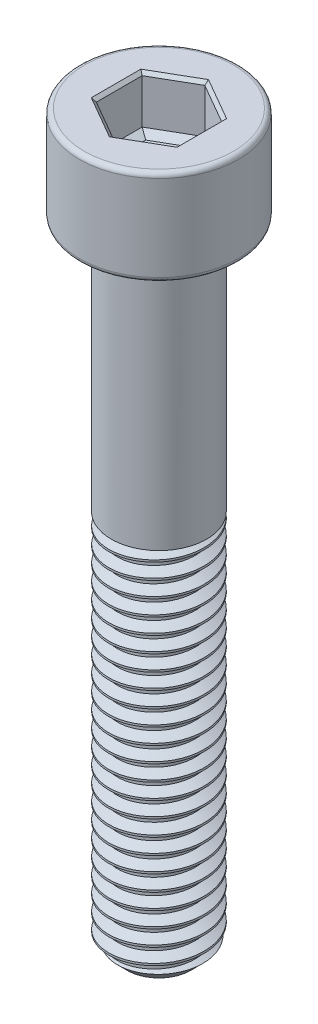
SolidWorks part; units mm, degrees
material "AISI Type A2 Tool Steel"
ref_plane "Front Plane" through (0, 0, 0) normal (0, 0, 1) x (1, 0, 0)
ref_plane "Top Plane" through (0, 0, 0) normal (0, 1, 0) x (1, 0, 0)
ref_plane "Right Plane" through (0, 0, 0) normal (1, 0, 0) x (0, 0, -1)
sketch "Sketch1" plane through (0, 0, 0) normal (0, 1, 0) x (1, 0, 0)
  circle A0 centre (0, 0) radius 3
  dimension "D1" = 6
extrude "Boss-Extrude1" add sketch "Sketch1" along normal blind 24
thread "Thread1" pitch 1 method cut profile "Thread Profile1" start angle 0, offset 1, length 0, pitch 1, diameter 6
ref_plane "Plane1" through (-3, 25, 0) normal (0, 0, 1) x (-1, 0, 0)
sketch "Thread Profile1" plane through (-3, 25, 0) normal (0, 0, 1) x (-1, 0, 0)
  line L0 (0, 0) -> (0, 1) construction
  line L11 (0, 0) -> (0, 0.875)
  line L12 (0, 0.875) -> (-0.5413, 0.5625)
  line L13 (-0.5413, 0.5625) -> (-0.5413, 0.3125)
  line L15 (-0.5413, 0.3125) -> (0, 0)
  line L17 (-0.5413, 0.4375) -> (0, 0.4375) construction
  point P2 (0, 0)
  dimension "Pitch" = 1
  dimension "Profile_Angle" = 60
  dimension "Profile_Land" = 0.25
  dimension "Profile_Height" = 0.5413
sketch "Sketch4" plane through (0, 24, 0) normal (0, 1, 0) x (1, 0, 0)
  circle A0 centre (0, 0) radius 3
  dimension "D1" = 6
extrude "Boss-Extrude2" add sketch "Sketch4" along normal blind 16
sketch "Sketch5" plane through (0, 40, 0) normal (0, 1, 0) x (1, 0, 0)
  circle A0 centre (0, 0) radius 5
  dimension "D1" = 10
extrude "Boss-Extrude3" add sketch "Sketch5" along normal blind 6
fillet "Fillet1" radius 0.3 2 edges at (0, 46, 5) (0, 40, 5)
sketch "Sketch6" plane through (0, 0, 0) normal (0, 0, 1) x (1, 0, 0)
  line L0 (0, 0) -> (0, 0.5449) construction
  line L1 (0, 0) -> (3.01, 0) construction
  line L2 (3.01, 0) -> (3.01, 1)
  line L3 (3.01, 1) -> (2.01, 0)
  line L4 (2.01, 0) -> (3.01, 0)
  dimension "D1" = 45
  dimension "D2" = 1
  dimension "D3" = 3.01
revolve "Cut-Revolve1" cut sketch "Sketch6" angle 360 about L0
sketch "Sketch7" plane through (0, 46, 0) normal (0, 1, 0) x (1, 0, 0)
  line L1 (0, 2.8868) -> (-2.5, 1.4434)
  line L2 (-2.5, 1.4434) -> (-2.5, -1.4434)
  line L3 (-2.5, -1.4434) -> (0, -2.8868)
  line L4 (0, -2.8868) -> (2.5, -1.4434)
  line L5 (2.5, -1.4434) -> (2.5, 1.4434)
  line L6 (2.5, 1.4434) -> (0, 2.8868)
  circle A0 centre (0, 0) radius 2.5 construction
  dimension "D1" = 5
extrude "Cut-Extrude1" cut sketch "Sketch7" against normal blind 3
chamfer "Chamfer1" distance 0.2 angle 45 6 edges at (-1.25, 46, 2.1651) (1.25, 46, 2.1651) (2.5, 46, 0) (1.25, 46, -2.1651) (-1.25, 46, -2.1651) (-2.5, 46, 0)
sketch "Sketch8" plane through (0, 43, 0) normal (0, 1, 0) x (1, 0, 0)
  line L1 (0, 2.8868) -> (-2.5, 1.4434)
  line L2 (-2.5, 1.4434) -> (-2.5, -1.4434)
  line L3 (-2.5, -1.4434) -> (0, -2.8868)
  line L4 (0, -2.8868) -> (2.5, -1.4434)
  line L5 (2.5, -1.4434) -> (2.5, 1.4434)
  line L6 (2.5, 1.4434) -> (0, 2.8868)
  circle A0 centre (0, 0) radius 2.5 construction
extrude "Cut-Extrude2" cut sketch "Sketch8" against normal blind 0.3 draft 60
